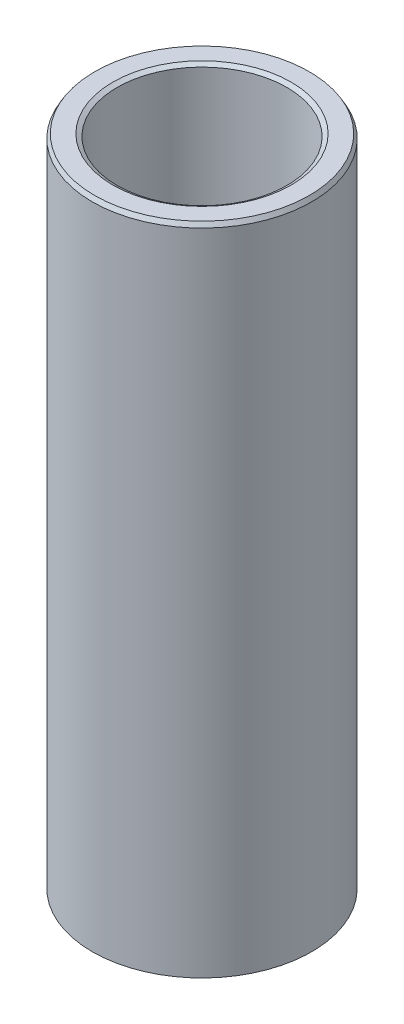
SolidWorks part; units mm, degrees
ref_plane "Front Plane" through (0, 0, 0) normal (0, 0, 1) x (1, 0, 0)
ref_plane "Top Plane" through (0, 0, 0) normal (0, 1, 0) x (1, 0, 0)
ref_plane "Right Plane" through (0, 0, 0) normal (1, 0, 0) x (0, 0, -1)
sketch "Sketch1" plane through (0, 0, 0) normal (0, 1, 0) x (1, 0, 0)
  circle A0 centre (0, 0) radius 45
  dimension "SLEEVE_OD" = 90
extrude "Boss-Extrude1" add sketch "Sketch1" along normal blind 269.0566
sketch "Sketch2" plane through (0, 0, 0) normal (0, 1, 0) x (1, 0, 0)
  circle A0 centre (0, 0) radius 34.8301
  dimension "BORE_D" = 69.6601
extrude "Cut-Extrude1" cut sketch "Sketch2" along normal through all
chamfer "Chamfer1" distance 1.7422 angle 30 4 edges at (0, 269.0566, 34.8301) (0, 0, 34.8301) (0, 0, 45) (0, 269.0566, 45) first distance on face at (0, 269.0566, 34.8301) first distance on face at (0, 0, 34.8301) first distance on face at (0, 269.0566, 45)
